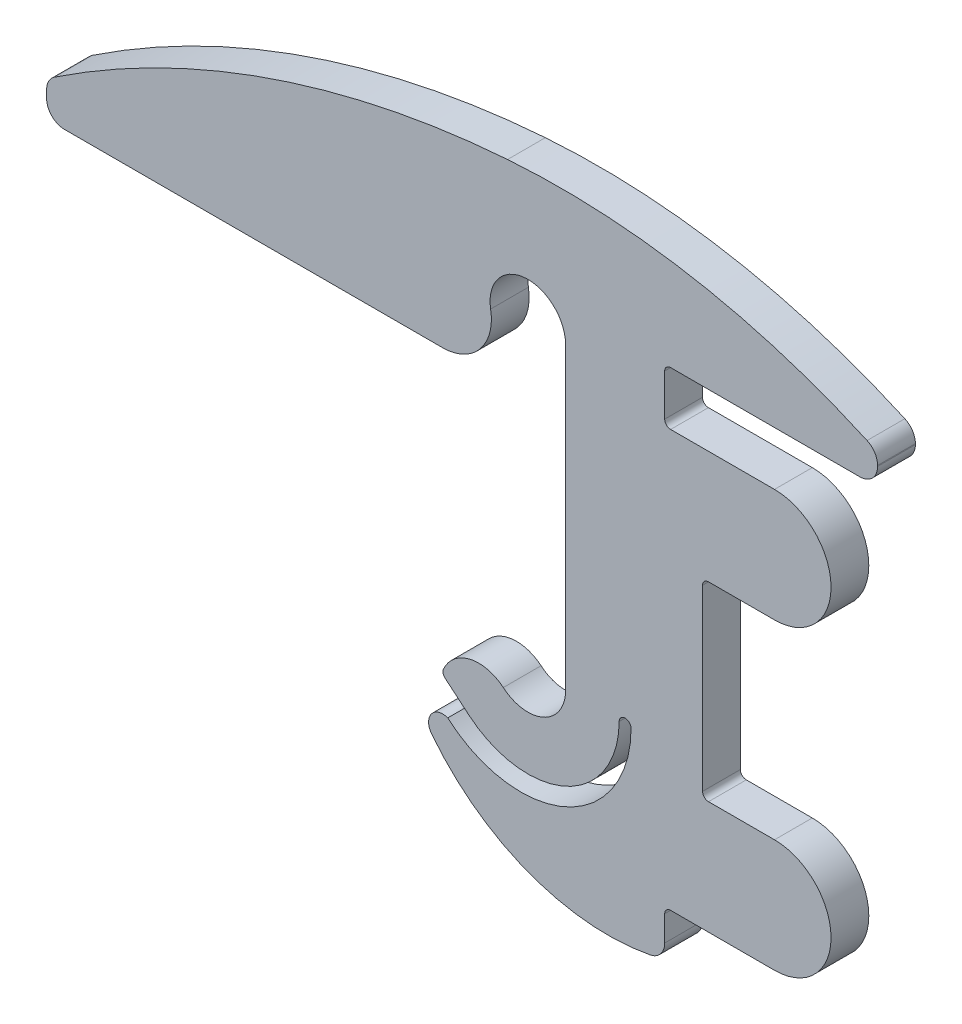
SolidWorks part; units mm, degrees
ref_plane "Front Plane" through (0, 0, 0) normal (0, 0, 1) x (1, 0, 0)
ref_plane "Top Plane" through (0, 0, 0) normal (0, 1, 0) x (1, 0, 0)
ref_plane "Right Plane" through (0, 0, 0) normal (1, 0, 0) x (0, 0, -1)
sketch "Model" plane through (0, 0, 0) normal (0, 0, 1) x (1, 0, 0)
  line L1 (14.6829, 1.325) -> (14.6829, -14.675)
  line L2 (29.3928, 17.8652) -> (29.3928, 15.325)
  line L3 (29.3928, 15.325) -> (11.5, 15.325)
  line L4 (11.5, 10.825) -> (11.5, 15.325)
  line L5 (20.7299, 10.825) -> (11.5, 10.825)
  line L6 (20.7299, 1.325) -> (14.6829, 1.325)
  line L7 (29.4125, -78.41) -> (15, -78.41) construction
  line L8 (15, -68.91) -> (26.4597, -68.91) construction
  line L9 (20.7299, -24.175) -> (11.5, -24.175)
  line L11 (15.1829, -68.5076) -> (15.1829, -53.2676) construction
  line L13 (12.3852, -39.41) -> (29.4597, -39.41) construction
  line L14 (14.6829, -14.675) -> (20.7299, -14.675)
  line L15 (11.5, -24.175) -> (11.5, -28.0042)
  line L16 (29.4125, -43.41) -> (15, -43.41) construction
  line L17 (12, -78.41) -> (12, -82.41) construction
  line L30 (-40.4406, 9.3328) -> (-40.4406, 8.6908)
  line L31 (-38.9406, 7.1908) -> (-7.182, 7.1908)
  line L32 (3.175, 12.575) -> (3.175, -12.575)
  line L33 (-7.2315, -16.526) -> (-4.9334, -18.4544)
  arc A0 (-1.7042, 23.6193) -> (29.3928, 17.8652) centre (2.8223, -38.8245) cw
  arc A1 (20.7299, 10.825) -> (20.7299, 1.325) centre (20.7299, 6.075) cw
  arc A2 (20.7299, -14.675) -> (20.7299, -24.175) centre (20.7299, -19.425) cw
  arc A3 (-8.0912, -21.3717) -> (11.5, -28.0042) centre (6.7381, -9.8191) ccw
  arc A4 (3.175, -12.575) -> (-2.0615, -14.9897) centre (0, -12.575) cw
  arc A5 (-4.9334, -18.4544) -> (7.675, -12.5941) centre (0, -12.575) ccw
  arc A6 (7.675, -12.5941) -> (8.675, -12.5954) centre (8.175, -12.5954) cw
  arc A7 (8.675, -12.5954) -> (-6.7315, -19.5356) centre (-0.5917, -12.5948) cw
  arc A8 (-8.0912, -21.3717) -> (-6.7315, -19.5356) centre (-7.1557, -20.643) cw
  arc A21 (-1.7042, 23.6193) -> (-39.7721, 10.5812) centre (4.0052, -55.1441) ccw
  arc A22 (-39.7721, 10.5812) -> (-40.4406, 9.3328) centre (-38.9406, 9.3328) ccw
  arc A23 (-40.4406, 8.6908) -> (-38.9406, 7.1908) centre (-38.9406, 8.6908) ccw
  arc A24 (-7.182, 7.1908) -> (-3.1268, 12.0237) centre (-7.182, 11.3086) ccw
  arc A25 (3.175, 12.575) -> (-3.1268, 12.0237) centre (0, 12.575) ccw
  arc A27 (-2.0615, -14.9897) -> (-7.2315, -16.526) centre (-4.1298, -17.4966) ccw
  dimension "D1" = 11.5
  dimension "D6" = 0.5
  dimension "D2" = 0.5
  dimension "D3" = 54.7349
  dimension "D4" = 54.2349
  dimension "D5" = 0.5
extrude "Boss-Extrude1" add sketch "Model" along normal blind 3.175
fillet "Fillet1" radius 0.5 6 edges at (-7.2315, -16.526, 1.5875) (11.5, -24.175, 1.5875) (14.6829, -14.675, 1.5875) (14.6829, 1.325, 1.5875) (11.5, 10.825, 1.5875) (11.5, 15.325, 1.5875)
sketch "Sketch3" plane through (0, 0, 0) normal (0, 0, -1) x (-1, 0, 0)
  circle A0 centre (-20.7299, -48.16) radius 0.9652
  circle A1 centre (-20.7299, -73.66) radius 0.9652
extrude "Cut-Extrude2" cut sketch "Sketch3" against normal up to next rebuild error yes
fillet "Fillet2" radius 1.5 3 edges at (11.5, -28.0042, 1.5875) (29.3928, 15.325, 1.5875) (29.3928, 17.8652, 1.5875)
